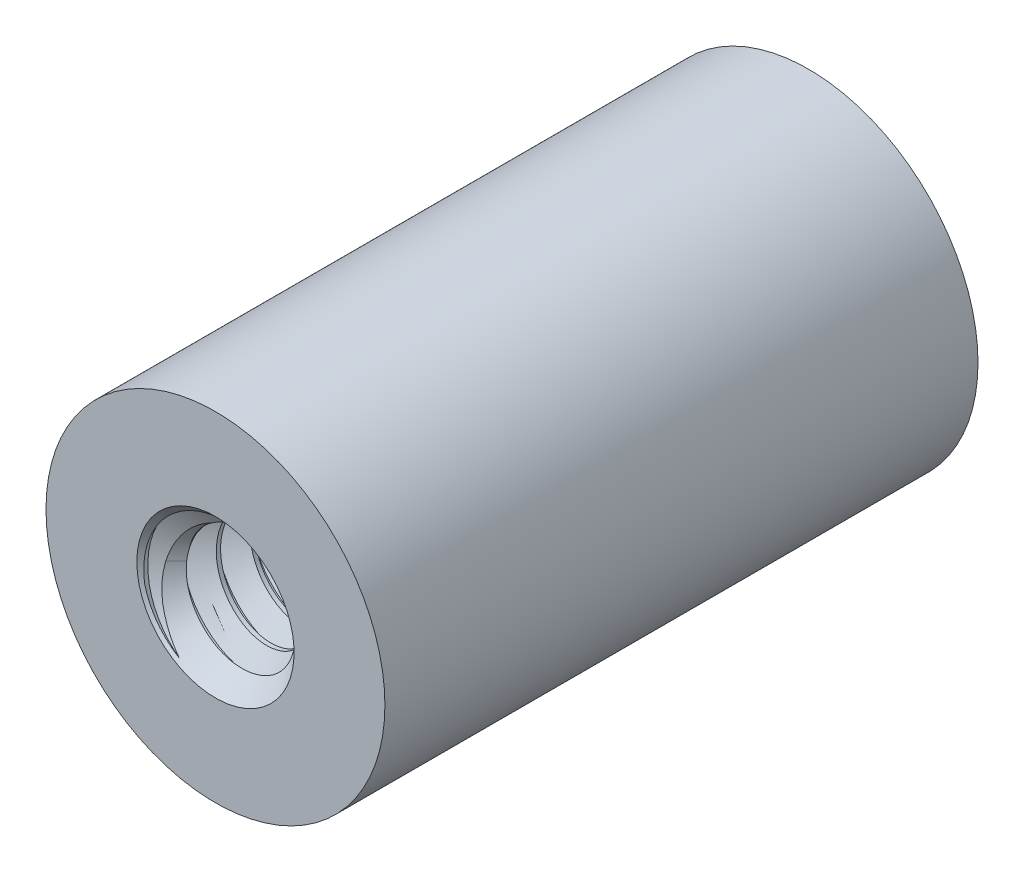
SolidWorks part; units mm, degrees
ref_plane "Front Plane" through (0, 0, 0) normal (0, 0, 1) x (1, 0, 0)
ref_plane "Top Plane" through (0, 0, 0) normal (0, 1, 0) x (1, 0, 0)
ref_plane "Right Plane" through (0, 0, 0) normal (1, 0, 0) x (0, 0, -1)
sketch "Sketch3" plane through (0, 0, 0) normal (1, 0, 0) x (0, 0, -1)
  line L0 (-5.5562, 0) -> (5.5562, 0) construction
  line L1 (0, 3.175) -> (0, -3.175) construction
  line L2 (-5.5562, 1.4224) -> (-5.5562, -1.4224) construction
  point P2 (-5.5562, 0)
  point P3 (5.5562, 0)
  dimension "Length" = 11.1125
  dimension "Min Thread Length" = 11.1125
  dimension "D1" = 11.1125
  dimension "Thread Dia" = 2.8448
  dimension "OD" = 6.35
sketch "Sketch1" plane through (0, 0, 0) normal (0, 0, 1) x (1, 0, 0)
  circle A1 centre (0, 0) radius 1.4224
  circle A2 centre (0, 0) radius 3.175
extrude "Extrude1" add sketch "Sketch1" along normal up to vertex (5.5563 mm away) and the other way up to vertex (5.5563 mm away) up to point (0, 0, 5.5562) other way up to point (0, 0, -5.5562)
sketch "Sketch11" plane through (0, 0, -5.5562) normal (0, 0, -1) x (-1, 0, 0)
  circle A0 centre (0, 0) radius 1.4224 construction
  circle A1 centre (0, 0) radius 1.4224
curve "Helix/Spiral1" pitch 0.635 height 11.7475 radius 1.4224 centre (0, 0, -5.5562) axis (0, 0, 1) start towards (0, 1, 0) parameters "Pitch"=0.635
sketch "Sketch12" plane through (0, 0, 0) normal (1, 0, 0) x (0, 0, -1)
  line L0 (6.1119, 1.4224) -> (5.5562, 1.4224)
  line L1 (6.1119, 1.4224) -> (5.8738, 1.01)
  line L2 (5.8738, 1.01) -> (5.7944, 1.01)
  line L3 (5.7944, 1.01) -> (5.5562, 1.4224)
  line L4 (5.8341, 1.01) -> (5.8341, 1.4224) construction
  line L5 (5.9928, 1.2162) -> (5.6753, 1.2162) construction
  dimension "D1" = 0.0794
  dimension "D2" = 0.3175
  dimension "D3" = 60
sweep "Sweep1" add profiles "Sketch12" path "Helix/Spiral1"
sketch "Sketch6" plane through (0, 0, -5.5562) normal (0, 0, -1) x (-1, 0, 0)
  circle A1 centre (0, 0) radius 3.175
  circle A2 centre (0, 0) radius 3.175
  dimension "D1" = 0
extrude "Extrude2" cut sketch "Sketch6" along normal through all
sketch "Sketch7" plane through (0, 0, -5.5562) normal (0, 0, -1) x (-1, 0, 0)
  circle A2 centre (0, 0) radius 1.4732
  circle A3 centre (0, 0) radius 1.4732
  dimension "D1" = 0.0508
extrude "Extrude3" cut sketch "Sketch7" against normal through all draft 43
mirror "Mirror1" about plane through (0, 0, 0) normal (0, 0, 1) of "Extrude2", "Extrude3"
equation "\"D1@Sketch3\" = \"Min Thread Length@Sketch3\""
equation "\"D3@Helix/Spiral1\" = \"Length@Sketch3\"+\"Pitch@Helix/Spiral1\""
equation "\"D1@Sketch12\" = \"Pitch@Helix/Spiral1\"*.125"
equation "\"D2@Sketch12\" = \"Pitch@Helix/Spiral1\"*.5"
